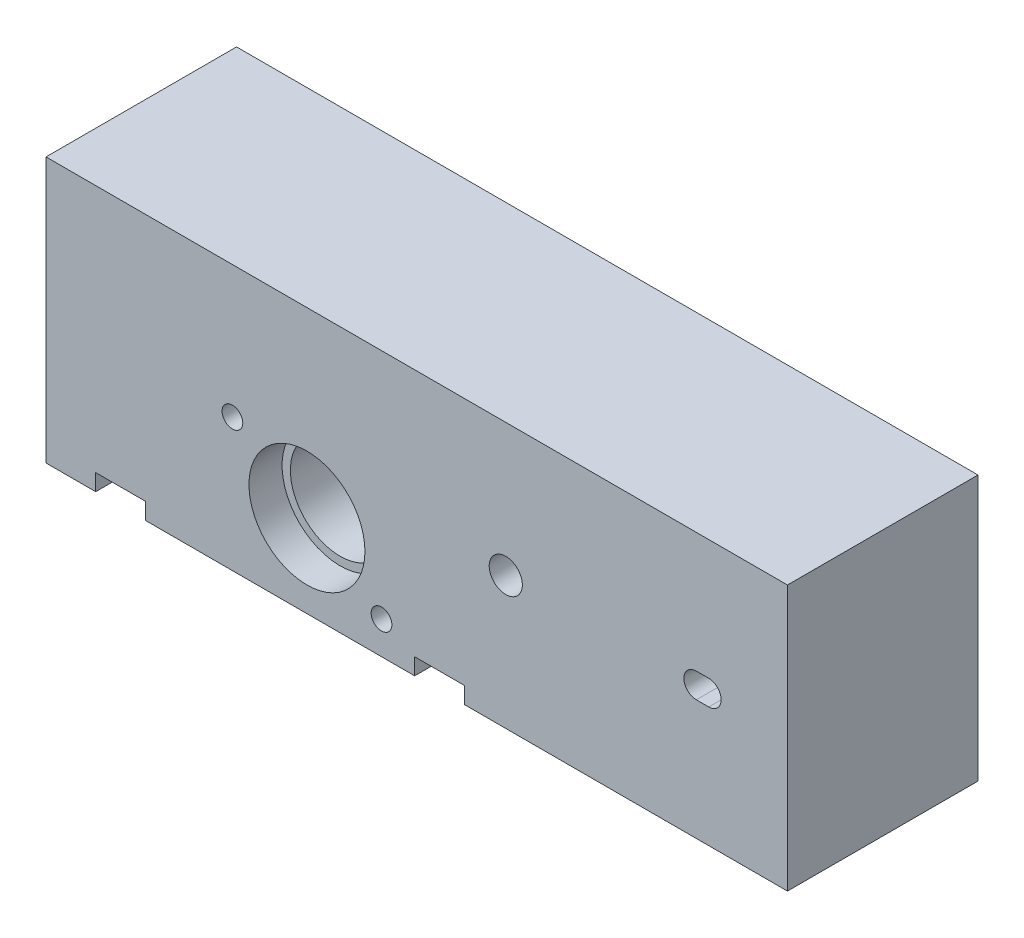
SolidWorks part; units mm, degrees
ref_plane "Front Plane" through (0, 0, 0) normal (0, 0, 1) x (1, 0, 0)
ref_plane "Top Plane" through (0, 0, 0) normal (0, 1, 0) x (1, 0, 0)
ref_plane "Right Plane" through (0, 0, 0) normal (1, 0, 0) x (0, 0, -1)
sketch "Sketch1" plane through (0, 0, 0) normal (0, 0, 1) x (1, 0, 0)
  line L1 (142.0813, 50.8) -> (-142.0812, 50.8)
  line L2 (142.0813, 50.8) -> (142.0813, -50.8)
  line L3 (142.0813, -50.8) -> (-142.0812, -50.8)
  line L4 (-142.0812, 50.8) -> (-142.0812, -50.8)
  line L5 (142.0813, 50.8) -> (-142.0812, -50.8) construction
  line L6 (142.0813, -50.8) -> (-142.0812, 50.8) construction
  point P0 (0, 0)
  dimension "D1" = 284.1625
  dimension "D2" = 101.6
extrude "Boss-Extrude1" add sketch "Sketch1" along normal blind 73.025
sketch "Sketch2" plane through (0, 0, 73.025) normal (0, 0, 1) x (1, 0, 0)
  line L0 (-142.0812, -50.8) -> (142.0813, -50.8) construction
  line L1 (-142.0812, 50.8) -> (-142.0812, -50.8) construction
  line L2 (107.1563, 0) -> (111.9188, 0) construction
  line L3 (107.1563, 4.7625) -> (111.9188, 4.7625)
  line L4 (107.1563, -4.7625) -> (111.9188, -4.7625)
  line L5 (-70.638, 0.1766) -> (-13.4995, -38.2766) construction
  circle A0 centre (-42.0687, -19.05) radius 19.05
  circle A1 centre (-42.0687, -19.05) radius 22.225
  circle A2 centre (34.1313, 0) radius 4.7625
  circle A3 centre (34.1313, 0) radius 6.35
  arc A4 (107.1563, 4.7625) -> (107.1563, -4.7625) centre (107.1563, 0) ccw
  arc A5 (111.9188, -4.7625) -> (111.9188, 4.7625) centre (111.9188, 0) ccw
  circle A6 centre (-13.4995, -38.2766) radius 3.9688
  circle A7 centre (-70.638, 0.1766) radius 3.9687
  point P12 (109.5375, 0)
  point P19 (-42.0687, -19.05)
  dimension "D1" = 38.1
  dimension "D2" = 44.45
  dimension "D5" = 9.525
  dimension "D7" = 4.7625
  dimension "D11" = 12.7
  dimension "D12" = 7.9375
  dimension "D3" = 31.75
  dimension "D4" = 100.0125
  dimension "D6" = 4.7625
  dimension "D8" = 73.025
  dimension "D9" = 76.2
  dimension "D10" = 50.8
extrude "Cut-Extrude1" cut sketch "Sketch2" against normal through all contours A0 | A2 | L4 A5 L3 A4 | A6 | A7 region at (109.5375, 0, 73.025) region at (-42.0687, -19.05, 73.025) region at (34.1313, 0, 73.025)
extrude "Cut-Extrude2" cut sketch "Sketch2<3>" against normal blind 12.7 contours A1 | A3
sketch "Sketch2<3>" plane through (0, 0, 73.025) normal (0, 0, 1) x (1, 0, 0) same geometry as "Sketch2"
sketch "Sketch3" plane through (0, 0, 0) normal (0, 0, -1) x (-1, 0, 0)
  line L0 (142.0812, -50.8) -> (-142.0813, -50.8) construction
  line L1 (123.0312, -50.8) -> (103.9812, -50.8)
  line L2 (123.0312, -50.8) -> (123.0312, -44.45)
  line L3 (123.0312, -44.45) -> (103.9812, -44.45)
  line L4 (103.9812, -50.8) -> (103.9812, -44.45)
  line L5 (142.0812, 50.8) -> (142.0812, -50.8) construction
  line L6 (0.7937, -50.8) -> (-18.2563, -50.8)
  line L7 (0.7937, -50.8) -> (0.7937, -44.45)
  line L8 (0.7937, -44.45) -> (-18.2563, -44.45)
  line L9 (-18.2563, -50.8) -> (-18.2563, -44.45)
  line L10 (-142.0813, 50.8) -> (142.0812, 50.8) construction
  line L11 (0.7937, 19.05) -> (-123.0313, 19.05)
  line L12 (0.7937, 19.05) -> (0.7937, -19.05)
  line L13 (0.7937, -19.05) -> (-123.0313, -19.05)
  line L14 (-123.0313, 19.05) -> (-123.0313, -19.05)
  line L15 (0.7937, 19.05) -> (-123.0313, -19.05) construction
  line L16 (0.7937, -19.05) -> (-123.0313, 19.05) construction
  line L17 (-142.0813, -50.8) -> (-142.0813, 50.8) construction
  point P12 (103.9812, -47.625)
  point P13 (-61.1188, 0)
  circle M9 centre (-34.1313, 0) radius 4.7625
  line M10 (-107.1563, -4.7625) -> (-111.9188, -4.7625)
  arc M11 (-111.9188, -4.7625) -> (-111.9188, 4.7625) centre (-111.9188, 0) cw
  line M12 (-111.9188, 4.7625) -> (-107.1563, 4.7625)
  arc M13 (-107.1563, 4.7625) -> (-107.1563, -4.7625) centre (-107.1563, 0) cw
  line M20 (-142.0813, -50.8) -> (142.0812, -50.8)
  dimension "D1" = 19.05
  dimension "D2" = 19.05
  dimension "D3" = 19.05
  dimension "D4" = 103.1875
  dimension "D5" = 6.35
  dimension "D6" = 38.1
  dimension "D7" = 123.825
  dimension "D8" = 31.75
  dimension "D9" = 19.05
extrude "Cut-Extrude3" cut sketch "Sketch3" against normal blind 31.75 contours L11 L14 L13 L12 M9 M13 M10 M11 M12 region at (60.2968, 0, 0)
extrude "Cut-Extrude4" cut sketch "Sketch3<3>" against normal through all contours L9 L7 L8 M20 | L4 L2 L3 M20 region at (8.7313, -47.625, 0) region at (-113.5062, -47.625, 0)
sketch "Sketch3<3>" plane through (0, 0, 0) normal (0, 0, -1) x (-1, 0, 0) same geometry as "Sketch3"
